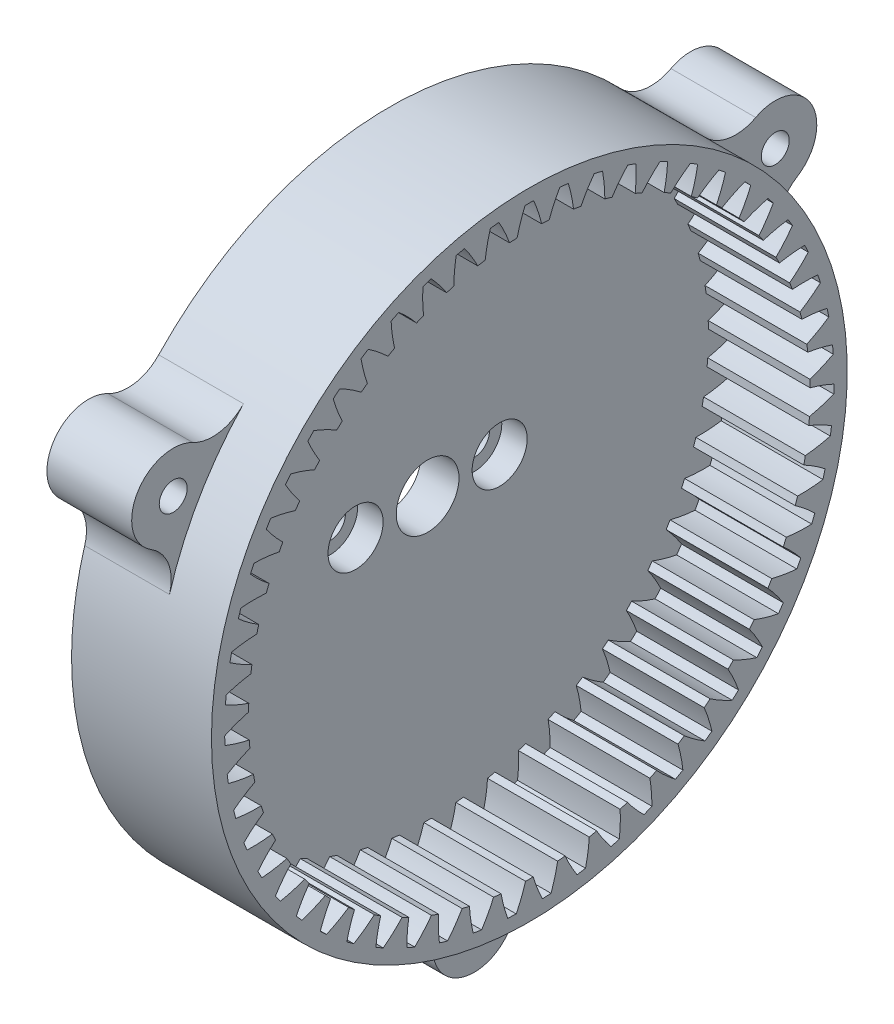
SolidWorks part; units mm, degrees
ref_plane "Plane1" through (0, 0, 0) normal (0, 0, 1) x (1, 0, 0)
ref_plane "Plane2" through (0, 0, 0) normal (0, 1, 0) x (1, 0, 0)
ref_plane "Plane3" through (0, 0, 0) normal (1, 0, 0) x (0, 0, -1)
sketch "HoldingSke" plane through (0, 0, 0) normal (0, 1, 0) x (1, 0, 0)
  line L0 (0, 0) -> (0.4589, -0.6553)
  line L1 (-15, 0) -> (100, 0) construction
  line L2 (0, 0) -> (-2.1039, 2.3779)
  line L3 (0, 0) -> (-11.863, 4.5341)
  line L4 (0, 0) -> (4.9534, 7.0742)
  line L5 (0, 0) -> (-23.7986, -8.8762)
  line L6 (0, 0) -> (-10.5278, -7.1032)
  line L7 (-2.1039, 2.3779) -> (3.3635, 27.1825)
  line L8 (-76.2, 3.6279) -> (-54.61, 3.6279)
  line L9 (-67.7845, 28.3722) -> (-49.3413, 33.142)
  line L10 (-76.2, 71.12) -> (104.1128, 71.12)
  line L11 (0, 0) -> (-12, 0)
  line L12 (-76.2, 101.6) -> (-76.155, 101.6)
  line L13 (24.9733, 27.94) -> (52.9518, 28.4284)
  line L14 (24.9733, 27.94) -> (24.9743, 27.94)
  line L15 (24.9733, 27.94) -> (100.4006, 29.5858)
  circle A0 centre (0, 0) radius 37.5
  circle A1 centre (0, 0) radius 12.7
  circle A2 centre (0, 0) radius 12.7
  dimension "MHD" = 25.4
  dimension "Hub_dia" = 25.4
  dimension "Diameter" = 75
  dimension "Num_teeth" = 55
  dimension "Pitch" = 0.8
  dimension "Overall_len" = 25.4
  dimension "Show_teeth" = 55
  dimension "Thickness" = 12.7
  dimension "OAL" = 25.4001
  dimension "T_dim" = 21.59
  dimension "Ap" = 14.5
  dimension "H" = 19.05
  dimension "Pitch_radius" = 180.3128
  dimension "Width" = 12
  dimension "Backlash" = 0.045
  dimension "Addendum_fac" = 1
  dimension "Dedendum_fac" = 1.25
  dimension "Clearance_fac" = 0.25
  dimension "Dedendum_add" = 0.001
  dimension "Module" = 1.25
sketch "BasProSke" plane through (0, 0, 0) normal (0, 1, 0) x (1, 0, 0)
  line L0 (-10, 0) -> (60, 0) construction
  line L1 (0, 33.125) -> (0, 37.5)
  line L2 (0, 33.125) -> (12, 33.125)
  line L3 (12, 33.125) -> (12, 37.5)
  line L4 (12, 37.5) -> (0, 37.5)
  dimension "Diameter" = 75
  dimension "Thickness" = 12
  dimension "Inside_diameter" = 66.25
revolve "Base-Revolve" add sketch "BasProSke" angle 360 about L0
sketch "TooCutSke" plane through (0, 0, 0) normal (1, 0, 0) x (0, 0, -1)
  line L3 (1.0941, 34.3576) -> (1.0941, 53.6633) construction
  line L4 (0, 0) -> (0, 59.563) construction
  line L5 (0, 0) -> (-3.9007, 68.2161) construction
  line L6 (-15.2783, 29.1274) -> (36.0712, 32.0636) construction
  circle A0 centre (0, 0) radius 34.375 construction
  circle A1 centre (0, 0) radius 35.9385 construction
  circle A2 centre (0, 0) radius 29.9521 construction
  circle A3 centre (0, 0) radius 33.0996 construction
  arc A4 (1.4514, 33.0678) -> (0.5036, 35.935) centre (-15.2783, 29.1274) ccw
  arc A5 (1.4514, 33.0678) -> (-1.4514, 33.0678) centre (0, 0) ccw
  arc A6 (0.5036, 35.935) -> (-0.5036, 35.935) centre (0, 0) ccw
  arc A7 (-0.5036, 35.935) -> (-1.4514, 33.0678) centre (15.2783, 29.1274) ccw
  dimension "Pitch_dia" = 68.75
  dimension "Base_dia" = 59.9041
  dimension "Root_dia" = 71.877
  dimension "Overcut_dia" = 66.1992
  dimension "Flank_rad" = 17.1875
  dimension "Half_ang" = 3.273
  dimension "Half_CT" = 1.0941
extrude "ToothCut" cut sketch "TooCutSke" along normal through all
fillet "Breaks" [suppressed] radius 0.125
fillet "RootFillets" [suppressed] radius 0.3135
pattern_circular "TeethCuts" count 55 every 6.545 about axis through (-10, 0, 0) along (1, 0, 0) of "RootFillets", "Breaks", "ToothCut"
sketch "Sketch2" plane through (0, 0, 0) normal (-1, 0, 0) x (0, 0, 1)
  circle A0 centre (0, 0) radius 37.5
extrude "Boss-Extrude2" add sketch "Sketch2" along normal blind 4.5
sketch "Sketch3" plane through (0, 0, 0) normal (1, 0, 0) x (0, 0, -1)
  circle A0 centre (0, 0) radius 3.7
  circle A1 centre (8.5, 0) radius 1.8
  circle A2 centre (-8.5, 0) radius 1.8
  dimension "D1" = 7.4
  dimension "D2" = 3.6
  dimension "D3" = 8.5
  dimension "D4" = 8.5
extrude "Cut-Extrude1" cut sketch "Sketch3" against normal blind 10 contours A1 | A0 | A2
sketch "Sketch4" plane through (0, 0, 0) normal (1, 0, 0) x (0, 0, -1)
  circle A0 centre (8.5, 0) radius 3.25
  circle A1 centre (-8.5, 0) radius 3.25
  dimension "D1" = 6.5
extrude "Cut-Extrude2" cut sketch "Sketch4" against normal blind 3
sketch "Sketch5" plane through (-4.5, 0, 0) normal (-1, 0, 0) x (0, 0, 1)
  line L0 (0, 0) -> (0, -41) construction
  line L1 (0, 0) -> (0, -45.9) construction
  circle A0 centre (0, -41) radius 1.65
  circle A1 centre (-35.507, 20.5) radius 1.65
  circle A2 centre (35.507, 20.5) radius 1.65
  arc A3 (3.2765, -37.3566) -> (-3.2765, -37.3566) centre (0, -41) cw
  circle A4 centre (0, 0) radius 37.5 construction
  arc A5 (3.2765, -37.3566) -> (-3.2765, -37.3566) centre (0, 0) cw
  arc A6 (-33.99, 15.8408) -> (-30.7135, 21.5158) centre (-35.507, 20.5) cw
  arc A7 (-33.99, 15.8408) -> (-30.7135, 21.5158) centre (0, 0) cw
  arc A8 (30.7135, 21.5158) -> (33.99, 15.8408) centre (35.507, 20.5) cw
  arc A9 (30.7135, 21.5158) -> (33.99, 15.8408) centre (0, 0) cw
  point P11 (0, 0)
  point P25 (0, 0)
  dimension "D1" = 3.3
  dimension "D5" = 3
  dimension "D2" = 41
  dimension "D4" = 45.9
  dimension "D3" = 3
extrude "Boss-Extrude3" add sketch "Sketch5" against normal blind 10
fillet "Fillet1" radius 5 6 edges at (0.5, 15.8408, -33.99) (0.5, 21.5158, -30.7135) (0.5, 21.5158, 30.7135) (0.5, 15.8408, 33.99) (0.5, -37.3566, 3.2765) (0.5, -37.3566, -3.2765)
equation "' \"Module@HoldingSke\" = 6.35"
equation "' \"Num_teeth@HoldingSke\" = 24"
equation "' \"Ap@HoldingSke\" =  14.5"
equation "' \"Ap@HoldingSke\" = 14.5"
equation "' \"Width@HoldingSke\" = 12"
equation "' \"Diameter@HoldingSke\" = 8 * 25.4"
equation "' \"Show_teeth@HoldingSke\" = 100"
equation "' \"Backlash@HoldingSke\" = 0.009 * 25.4"
equation "' \"Addendum_fac@HoldingSke\" = 1.0"
equation "' \"Dedendum_fac@HoldingSke\" = 1.25"
equation "' \"Dedendum_add@HoldingSke\" = 0.00005 * 25.4"
equation "' \"Clearance_fac@HoldingSke\" = 0.25"
equation "\"Pitch@HoldingSke\" = 1 / \"Module@HoldingSke\" "
equation "\"Overcut_dia@TooCutSke\" = (\"Num_teeth@HoldingSke\" - 2 * \"Addendum_fac@HoldingSke\") / \"Pitch@HoldingSke\" - 0.002 * 25.4"
equation "\"Pitch_dia@TooCutSke\" = \"Num_teeth@HoldingSke\" / \"Pitch@HoldingSke\""
equation "\"Base_dia@TooCutSke\" = \"Num_teeth@HoldingSke\" / \"Pitch@HoldingSke\" * cos((\"Ap@HoldingSke\"  * 3.14159265 / 180)) * 0.90"
equation "\"Root_dia@TooCutSke\" = \"Num_teeth@HoldingSke\"  / \"Pitch@HoldingSke\" + 2 *  \"Dedendum_fac@HoldingSke\"/ \"Pitch@HoldingSke\" + \"Dedendum_add@HoldingSke\" * 2"
equation "\"Half_ang@TooCutSke\" = 180 / \"Num_teeth@HoldingSke\""
equation "\"Half_CT@TooCutSke\" = \"Num_teeth@HoldingSke\" / \"Pitch@HoldingSke\" * sin((3.14159265 / 2 / \"Num_teeth@HoldingSke\")) / 2 + 10 * \"Backlash@HoldingSke\" / 4"
equation "\"Flank_rad@TooCutSke\" = \"Num_teeth@HoldingSke\" / \"Pitch@HoldingSke\" / 4"
equation "\"Radius@RootFillets\"= \"Clearance_fac@HoldingSke\" / \"Pitch@HoldingSke\" + \"Dedendum_add@HoldingSke\""
equation "\"Break_rad@Breaks\" = 0.02 / \"Pitch@HoldingSke\" * 5"
equation "\"Num_teeth@TeethCuts\" = int( \"Show_teeth@HoldingSke\" ) + 1"
equation "\"Num_teeth@TeethCuts\" = ((sgn( \"Num_teeth@TeethCuts\" - \"Num_teeth@HoldingSke\" )-1)*( \"Num_teeth@TeethCuts\" - \"Num_teeth@HoldingSke\" ))/-2+ \"Num_teeth@HoldingSke\""
equation "\"Num_teeth@TeethCuts\" = ((sgn( \"Num_teeth@TeethCuts\" - 2.0)+1)*( \"Num_teeth@TeethCuts\" - 2.0))/2 +2.0"
equation "\"Angle@TeethCuts\" = 360.0 / \"Num_teeth@HoldingSke\""
equation "\"Diameter@BasProSke\" = \"Num_teeth@HoldingSke\"  / \"Pitch@HoldingSke\" + 2 *  \"Dedendum_fac@HoldingSke\"/ \"Pitch@HoldingSke\" + \"Dedendum_add@HoldingSke\" * 2 + 0.002 * 25.4"
equation "\"Diameter@BasProSke\" = ((sgn( \"Diameter@BasProSke\"  - \"Diameter@HoldingSke\" )+1)*( \"Diameter@BasProSke\"  - \"Diameter@HoldingSke\" ))/2 + \"Diameter@HoldingSke\""
equation "\"Inside_diameter@BasProSke\" =  (\"Num_teeth@HoldingSke\" - 2 * \"Addendum_fac@HoldingSke\") / \"Pitch@HoldingSke\" "
equation "\"Thickness@BasProSke\"  = \"Width@HoldingSke\""
